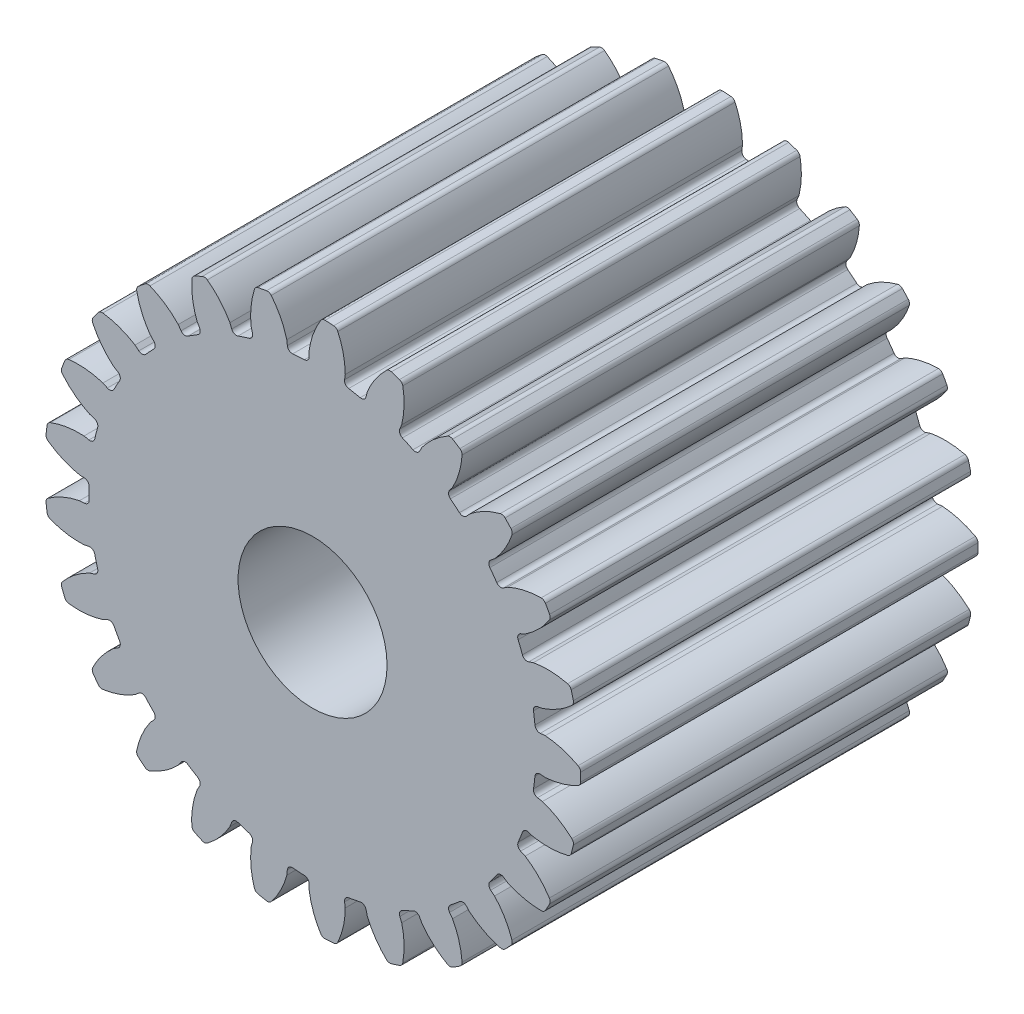
SolidWorks part; units mm, degrees
material "Нержавеющая сталь (ферритная)"
ref_plane "Спереди" through (0, 0, 0) normal (0, 0, 1) x (1, 0, 0)
ref_plane "Сверху" through (0, 0, 0) normal (0, 1, 0) x (1, 0, 0)
ref_plane "Справа" through (0, 0, 0) normal (1, 0, 0) x (0, 0, -1)
sketch "Эскиз1" plane through (0, 0, 0) normal (0, 0, 1) x (1, 0, 0)
  circle A0 centre (0, 0) radius 4.5
  circle A1 centre (0, 0) radius 1.5
  dimension "D1" = 9
  dimension "D2" = 3
extrude "Бобышка-Вытянуть1" add sketch "Эскиз1" along normal mid plane 8
sketch "Эскиз2" plane through (0, 0, 0) normal (0, 0, 1) x (1, 0, 0)
  line L0 (0, 0) -> (0, 5) construction
  line L1 (0, 5) -> (0.6183, 5) construction
  line L2 (0, 5) -> (1.607, 4.4151) construction
  line L3 (2.4622, 4.0016) -> (0.1953, 5.3965) construction
  line L4 (0, 0) -> (-0.07, 4.6979) construction
  line L5 (-0.07, 4.6979) -> (-0.0671, 4.4995)
  line L6 (0, 0) -> (0.3391, 5.3893) construction
  line L7 (0.6583, 4.6521) -> (0.6305, 4.4556)
  arc A0 (0.4826, 5.3784) -> (0.1953, 5.3965) centre (0, 0) ccw
  circle A1 centre (0, 0) radius 5 construction
  circle A2 centre (0, 0) radius 4.5 construction
  arc A3 (0.6305, 4.4556) -> (-0.0671, 4.4995) centre (0, 0) ccw
  circle A4 centre (0, 0) radius 4.6985 construction
  spline S0 degree 2 poles (-0.07, 4.6979) (-0.0186, 5.0762) (0.1953, 5.3965) knots 0 0 0 1 1 1
  spline S1 degree 2 poles (0.6583, 4.6521) (0.6547, 5.0338) (0.4826, 5.3784) knots 0 0 0 1 1 1
  point P10 (1.607, 4.4151)
  point P11 (-0.07, 4.6979)
  dimension "D1" = 10
  dimension "D2" = 10.8
  dimension "D3" = 20
  dimension "D4" = 1.7101
  dimension "D6" = 2.6617
  dimension "D8" = 3.6
  dimension "D5" = 1.7101
  dimension "D7" = 0.9516
extrude "Бобышка-Вытянуть2" add sketch "Эскиз2" along normal mid plane 8
fillet "Скругление1" radius 0.1 4 edges at (-0.0671, 4.4995, 0) (0.6305, 4.4556, 0) (0.4826, 5.3784, 0) (0.1953, 5.3965, 0)
pattern_circular "Круговой массив1" count 25 over 360 about axis through (0, 0, 4) along (0, 0, -1) of "Бобышка-Вытянуть2", "Скругление1"
equation "\"Число зубьев\"= 25"
equation "\"Модуль\"= 0.4мм"
equation "\"D1@Эскиз1\"= \"Модуль\" * (\"Число зубьев\" - 2.5)"
equation "\"D1@Эскиз2\"= \"Модуль\" * \"Число зубьев\""
equation "\"D5@Эскиз2\"= \"D4@Эскиз2\""
equation "\"D7@Эскиз2\"= \"D6@Эскиз2\" - \"D4@Эскиз2\""
equation "\"D8@Эскиз2\"= 90 / \"Число зубьев\""
equation "\"D1@Круговой массив1\"= \"Число зубьев\""
equation "\"D2@Эскиз2\"= \"Модуль\" * (\"Число зубьев\" + 2)"
